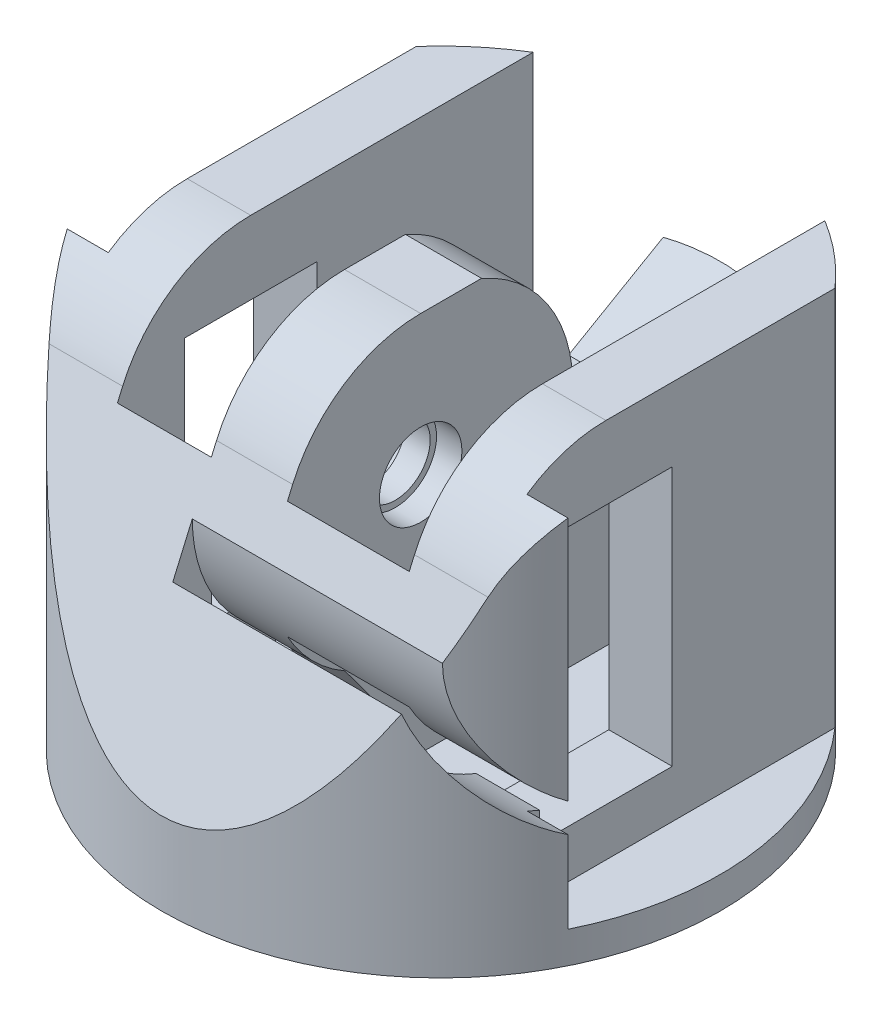
SolidWorks part; units mm, degrees
ref_plane "前视基准面" through (0, 0, 0) normal (0, 0, 1) x (1, 0, 0)
ref_plane "上视基准面" through (0, 0, 0) normal (0, 1, 0) x (1, 0, 0)
ref_plane "右视基准面" through (0, 0, 0) normal (1, 0, 0) x (0, 0, -1)
sketch "草图1" plane through (0, 0, 0) normal (0, 1, 0) x (1, 0, 0)
  circle A0 centre (0, 0) radius 44
  dimension "D1" = 88
extrude "凸台-拉伸1" add sketch "草图1" along normal blind 80
sketch "草图2" plane through (0, 0, 0) normal (0, 1, 0) x (1, 0, 0)
  line L0 (33, 29.1033) -> (33, -19.45)
  line L1 (33, -19.45) -> (39.4677, -19.45)
  line L2 (36.6, -16.45) -> (56.9, -16.45) construction
  line L3 (0, 44) -> (0, -28)
  line L4 (0, -28) -> (23, -28)
  line L5 (23, -28) -> (23, 44)
  line L6 (23, 44) -> (0, 44)
  circle A1 centre (0, 0) radius 44 construction
  arc A2 (39.4677, -19.45) -> (33, 29.1033) centre (0, 0) ccw
  dimension "D1" = 33
  dimension "D2" = 3
  dimension "D3" = 10
  dimension "D4" = 28
extrude "切除-拉伸5" cut sketch "草图2" along normal through all from offset 5
mirror "镜向1" about plane through (0, 0, 0) normal (1, 0, 0) of "切除-拉伸5"
sketch "草图3" plane through (33, 0, 0) normal (1, 0, 0) x (0, 0, -1)
  line L0 (-16.45, 52.95) -> (2.45, 52.95) construction
  line L1 (-17.45, 53.45) -> (3.45, 53.45)
  line L2 (-17.45, 53.45) -> (-17.45, 12.55)
  line L3 (-17.45, 12.55) -> (3.45, 12.55)
  line L4 (3.45, 53.45) -> (3.45, 12.55)
  line L5 (-16.95, 52.45) -> (-16.95, 13.55) construction
  line L6 (2.95, 52.45) -> (2.95, 13.55) construction
  line L7 (-16.45, 13.05) -> (2.45, 13.05) construction
  dimension "D1" = 0.5
  dimension "D2" = 0.5
  dimension "D3" = 0.5
  dimension "D4" = 0.5
extrude "切除-拉伸6" cut sketch "草图3" against normal through all
sketch "草图6" plane through (0, 5, 0) normal (0, 1, 0) x (1, 0, 0)
  line L0 (-8.2, 43.2292) -> (-8.2, -28)
  line L1 (-23, -28) -> (23, -28) construction
  line L2 (3.8, 43.8356) -> (3.8, -28)
  line L3 (-12.2, -11.2) -> (-12.2, -2.8) construction
  line L6 (-23, 37.51) -> (-23, -28)
  line L7 (-23, -28) -> (23, -28)
  line L8 (23, -28) -> (23, 37.51)
  line L10 (-8.2, -28) -> (3.8, -28)
  arc A0 (23, 37.51) -> (-23, 37.51) centre (0, 0) ccw construction
  arc A2 (23, 37.51) -> (-23, 37.51) centre (0, 0) ccw
  arc A3 (3.8, 43.8356) -> (-8.2, 43.2292) centre (0, 0) ccw
  dimension "D2" = 4
  dimension "D3" = 12
  dimension "D1" = 0
extrude "凸台-拉伸2" add sketch "草图6" along normal up to surface (75 mm away) up to face at (0, 80, 2.4377)
sketch "草图7" plane through (3.8, 0, 0) normal (1, 0, 0) x (0, 0, -1)
  circle A0 centre (-7, 43) radius 6.5
  dimension "D1" = 13
extrude "切除-拉伸7" cut sketch "草图7" against normal blind 4
sketch "草图8" plane through (-8.2, 0, 0) normal (-1, 0, 0) x (0, 0, 1)
  circle A0 centre (7, 43) radius 6.5 construction
  circle A1 centre (7, 43) radius 6.5
extrude "切除-拉伸8" cut sketch "草图8" against normal blind 4
sketch "草图9" plane through (3.8, 0, 0) normal (1, 0, 0) x (0, 0, -1)
  circle A0 centre (-7, 43) radius 5.5
  dimension "D1" = 11
extrude "切除-拉伸9" cut sketch "草图9" against normal up to next
sketch "草图10" plane through (33, 0, 0) normal (1, 0, 0) x (0, 0, -1)
  line L0 (44, 80) -> (44, 65)
  line L1 (44, 80) -> (43.2292, 80) construction
  line L2 (44, 0) -> (44, 80) construction
  line L3 (44, 65) -> (-7, 65)
  line L4 (-27.1818, 51.7576) -> (-44, 13)
  line L5 (-44, 80) -> (-44, 0) construction
  line L6 (-44, 13) -> (-44, 80)
  line L7 (-44, 80) -> (44, 80)
  arc A0 (-7, 65) -> (-27.1818, 51.7576) centre (-7, 43) ccw
  dimension "D1" = 22
  dimension "D2" = 13
extrude "切除-拉伸10" cut sketch "草图10" against normal through all both and the other way through all
ref_plane "基准面1" through (0, 43, 0) normal (0, 1, 0) x (1, 0, 0)
sketch "草图18" plane through (-8.2, 0, 0) normal (-1, 0, 0) x (0, 0, 1)
  line L0 (7, 43) -> (-13.7846, 55)
  line L1 (7, 43) -> (-28.9915, 43.7841)
  line L2 (7, 65) -> (-43.2292, 65) construction
  line L4 (7, 43) -> (7, 63.2759) construction
  line L5 (-2.5917, 65) -> (-21.4956, 65)
  circle A4 centre (7, 43) radius 24
  circle A5 centre (7, 43) radius 36
  point P3 (-2.5917, 65)
  point P9 (-21.4956, 65)
  line M9 (7, 65) -> (-43.2292, 65)
  dimension "D1" = 48
  dimension "D2" = 72
  dimension "D3" = 28.752
  dimension "D4" = 60
extrude "切除-拉伸13" cut sketch "草图18" against normal up to next contours A5 L1 A4 M9 region at (-8.2, 55.0577, -19.2929)
sketch "草图19" plane through (-8.2, 0, 0) normal (-1, 0, 0) x (0, 0, 1)
  line L0 (-13.7846, 55) -> (-25.7846, 34.2154)
  line L1 (-13.7846, 55) -> (7, 43)
  line L2 (-25.7846, 34.2154) -> (-75.1569, 62.7205)
  line L3 (7, 43) -> (7, 62.5327) construction
  line L4 (-75.1569, 62.7205) -> (-75.1569, 93.8418)
  line L5 (-75.1569, 93.8418) -> (-13.7846, 93.8418)
  line L6 (-13.7846, 93.8418) -> (-13.7846, 55)
  line M10 (-16.9943, 43.5227) -> (-28.9915, 43.7841)
  arc M11 (-28.9915, 43.7841) -> (-21.4956, 65) centre (7, 43) cw
  line M12 (-21.4956, 65) -> (-43.2292, 65)
  line M13 (-43.2292, 65) -> (-43.2292, 5)
  dimension "D1" = 24
  dimension "D2" = 24
  dimension "D3" = 60
extrude "切除-拉伸14" cut sketch "草图19" against normal up to next contours L2 L0 M10 M11 M12 M13 | L6 L5 L4 L2 L0 M13 M12 M11 M10 region at (-8.2, 73.6173, -43.7686) region at (-8.2, 51.8368, -33.5377)
sketch "草图21" plane through (-8.2, 0, 0) normal (-1, 0, 0) x (0, 0, 1)
  line L0 (44, 13) -> (27.1818, 51.7576) construction
  line L1 (34.0766, 35.8685) -> (31, 42.9586)
  line L2 (14.3622, 15.9852) -> (18.9641, 22.1947)
  circle A0 centre (7, 43) radius 24
  circle A1 centre (7, 43) radius 28
  point P6 (31, 42.9586)
  point P10 (34.0766, 35.8685)
  point P15 (7, 43)
  line M7 (28, 5) -> (28, 49.872)
  dimension "D1" = 48
  dimension "D2" = 56
  dimension "D3" = 2
extrude "切除-拉伸15" cut sketch "草图21" against normal up to next contours L2 A1 A0 M7 | A1 L1 A0 M7 region at (-8.2, 33.2277, 30.791) region at (-8.2, 22.6431, 22.6313)
